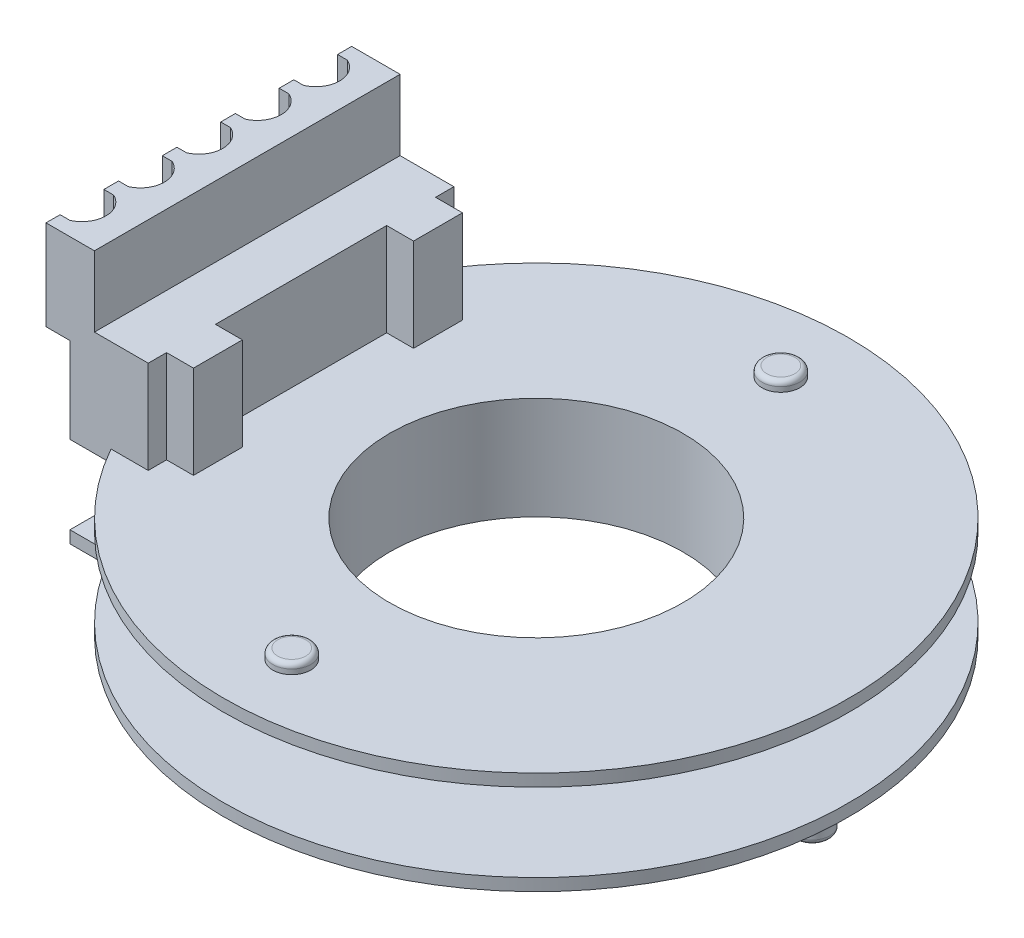
SolidWorks part; units mm, degrees
material "Полиамид ПА-6Б ТУ 6-05-988-93"
ref_plane "Спереди" through (0, 0, 0) normal (0, 0, 1) x (1, 0, 0)
ref_plane "Сверху" through (0, 0, 0) normal (0, 1, 0) x (1, 0, 0)
ref_plane "Справа" through (0, 0, 0) normal (1, 0, 0) x (0, 0, -1)
sketch "Эскиз1" plane through (0, 0, 0) normal (0, 0, 1) x (1, 0, 0)
  line L0 (7, 1.6) -> (7, -1.6)
  line L1 (7, -1.6) -> (12.775, -1.6)
  line L2 (12.775, -1.6) -> (12.775, -2.1)
  line L3 (12.775, -2.1) -> (6, -2.1)
  line L4 (6, -2.1) -> (6, 2.1)
  line L5 (6, 2.1) -> (12.775, 2.1)
  line L6 (12.775, 2.1) -> (12.775, 1.6)
  line L7 (12.775, 1.6) -> (7, 1.6)
  line L8 (6, 0) -> (0, 0) construction
  line L9 (0, 2.1) -> (0, -2.1) construction
  dimension "D1" = 6
  dimension "D2" = 0.5
  dimension "D3" = 1
  dimension "D4" = 4.2
  dimension "D5" = 12.775
revolve "Повернуть1" add sketch "Эскиз1" angle 360 about L9
sketch "Эскиз2" plane through (0, 2.1, 0) normal (0, 1, 0) x (1, 0, 0)
  line L0 (-12.82, 6.25) -> (-9.47, 6.25)
  line L1 (-9.47, 6.25) -> (-9.47, -6.25)
  line L2 (-9.47, -6.25) -> (-12.82, -6.25)
  line L5 (-12.82, -6.25) -> (-12.82, 6.25)
  line L8 (-9.47, 0) -> (0, 0) construction
  dimension "D2" = 12.5
  dimension "D4" = 3.35
  dimension "D5" = 9.47
extrude "Бобышка-Вытянуть1" add sketch "Эскиз2" along normal blind 3.8 and the other way blind 0.5
sketch "Эскиз4" plane through (0, 5.9, 0) normal (0, 1, 0) x (1, 0, 0)
  line L0 (-12.82, 6.25) -> (-12.82, -6.25) construction
  line L1 (-9.47, 6.25) -> (-8.52, 6.25)
  line L2 (-9.47, 6.25) -> (-9.47, -6.25)
  line L3 (-9.47, -6.25) -> (-8.52, -6.25)
  line L4 (-8.52, 6.25) -> (-8.52, -6.25)
  dimension "D1" = 4.3
extrude "Бобышка-Вытянуть2" add sketch "Эскиз4" against normal up to surface (3.8 mm away) up to face at (-6, 2.1, 0)
sketch "Эскиз6" plane through (0, 5.9, 0) normal (0, 1, 0) x (1, 0, 0)
  line L0 (-8.52, -6.25) -> (-8.52, 6.25) construction
  line L1 (-8.52, 6.25) -> (-9.62, 6.25)
  line L2 (-8.52, 6.25) -> (-8.52, 5.5)
  line L3 (-8.52, 5.5) -> (-9.62, 5.5)
  line L4 (-9.62, 6.25) -> (-9.62, 5.5)
  line L5 (-8.52, 3.5) -> (-9.62, 3.5)
  line L6 (-8.52, 3.5) -> (-8.52, -3.5)
  line L7 (-8.52, -3.5) -> (-9.62, -3.5)
  line L8 (-9.62, 3.5) -> (-9.62, -3.5)
  line L9 (-8.52, 0) -> (0, 0) construction
  line L10 (-8.52, -6.25) -> (-9.62, -6.25)
  line L11 (-8.52, -6.25) -> (-8.52, -5.5)
  line L12 (-8.52, -5.5) -> (-9.62, -5.5)
  line L13 (-9.62, -6.25) -> (-9.62, -5.5)
  point P19 (-8.52, 5.875)
  dimension "D1" = 2
  dimension "D2" = 0.75
  dimension "D3" = 1.1
extrude "Вырез-Вытянуть1" cut sketch "Эскиз6" against normal up to surface (3.8 mm away) up to face at (-6, 2.1, 0)
sketch "Эскиз7" plane through (0, 5.9, 0) normal (0, 1, 0) x (1, 0, 0)
  line L0 (-9.62, 6.25) -> (-12.82, 6.25) construction
  line L1 (-11.82, 6.25) -> (-13.8, 6.25)
  line L2 (-11.82, 6.25) -> (-11.82, -6.25)
  line L3 (-11.82, -6.25) -> (-13.8, -6.25)
  line L4 (-13.8, 6.25) -> (-13.8, -6.25)
  line L5 (-12.82, -6.25) -> (-9.62, -6.25) construction
  line L6 (-8.52, 3.5) -> (-8.52, 5.5) construction
  dimension "D1" = 3.3
  dimension "D2" = 1.98
extrude "Бобышка-Вытянуть3" add sketch "Эскиз7" along normal blind 2.88 and the other way blind 0.8
sketch "Эскиз8" plane through (-12.82, 0, 0) normal (-1, 0, 0) x (0, 0, 1)
  line L0 (-6.25, 1.6) -> (6.25, 1.6) construction
  circle A0 centre (-2.4, 2.45) radius 0.425
  circle A1 centre (0, 2.45) radius 0.425
  circle A2 centre (2.4, 2.45) radius 0.425
  dimension "D1" = 0.85
  dimension "D2" = 2.4
  dimension "D3" = 2.4
  dimension "D4" = 0.85
extrude "Бобышка-Вытянуть4" add sketch "Эскиз8" along normal blind 2.4 separate body
sketch "Эскиз9" plane through (0, 8.78, 0) normal (0, 1, 0) x (1, 0, 0)
  line L1 (-13.8, 6.25) -> (-13.8, -6.25) construction
  line L2 (-12.82, 6.25) -> (-12.82, -6.25) construction
  line L3 (-13.4, 3.284) -> (-13.8, 3.284)
  line L4 (-13.4, -1.4947) -> (-13.8, -1.4947)
  line L5 (-13.8, -1.4947) -> (-13.8, -3.284)
  line L6 (-13.4, 0.8947) -> (-13.8, 0.8947)
  line L7 (-13.8, 0.8947) -> (-13.8, -0.8947)
  line L8 (-13.4, 5.6733) -> (-13.8, 5.6733)
  line L9 (-13.8, 5.6733) -> (-13.8, 3.884)
  line L10 (-13.8, 3.884) -> (-13.4, 3.884)
  line L11 (-13.8, 3.284) -> (-13.8, 1.4947)
  line L12 (-13.8, 1.4947) -> (-13.4, 1.4947)
  line L13 (-13.8, -0.8947) -> (-13.4, -0.8947)
  line L14 (-13.8, -3.284) -> (-13.4, -3.284)
  line L15 (-13.4, -3.884) -> (-13.8, -3.884)
  line L16 (-13.8, -3.884) -> (-13.8, -5.6733)
  line L17 (-13.8, -5.6733) -> (-13.4, -5.6733)
  arc A0 (-13.4, 3.884) -> (-13.4, 5.6733) centre (-13.8, 4.7786) ccw
  arc A1 (-13.4, 1.4947) -> (-13.4, 3.284) centre (-13.8, 2.3893) ccw
  arc A2 (-13.4, -0.8947) -> (-13.4, 0.8947) centre (-13.8, 0) ccw
  arc A3 (-13.4, -3.284) -> (-13.4, -1.4947) centre (-13.8, -2.3893) ccw
  arc A4 (-13.4, -5.6733) -> (-13.4, -3.884) centre (-13.8, -4.7786) ccw
  dimension "D1" = 0.6
  dimension "D2" = 0.6
  dimension "D3" = 0.6
  dimension "D4" = 0.6
  dimension "D5" = 0.4
extrude "Вырез-Вытянуть2" cut sketch "Эскиз9" against normal up to surface (3.68 mm away) up to face at (-13.31, 5.1, 0)
sketch "Эскиз10" plane through (0, 2.1, 0) normal (0, 1, 0) x (1, 0, 0)
  circle A0 centre (0, 0) radius 10 construction
  circle A1 centre (0, 10) radius 0.775
  circle A2 centre (0, -10) radius 0.775
  dimension "D1" = 20
  dimension "D2" = 1.55
extrude "Бобышка-Вытянуть5" add sketch "Эскиз10" along normal blind 0.4
sketch "Эскиз11" plane through (0, -2.1, 0) normal (0, -1, 0) x (1, 0, 0)
  line L0 (-11.22, 5.35) -> (-11.22, -5.35) construction
  line L1 (-11.22, 0) -> (0, 0) construction
  circle A0 centre (0, -10) radius 0.775 construction
  circle A1 centre (0, 10) radius 0.775 construction
  circle A2 centre (0, -10) radius 0.775
  circle A3 centre (0, 10) radius 0.775
  circle A4 centre (11.28, 0) radius 0.725
  circle A5 centre (-11.22, 5.35) radius 0.725
  circle A6 centre (-11.22, -5.35) radius 0.725
  dimension "D3" = 1.45
  dimension "D1" = 11.22
  dimension "D2" = 10.7
  dimension "D4" = 11.28
extrude "Бобышка-Вытянуть6" add sketch "Эскиз11" along normal blind 0.4
sketch "Эскиз12" plane through (0, -2.5, 0) normal (0, -1, 0) x (1, 0, 0)
  circle A0 centre (11.28, 0) radius 0.725 construction
  circle A1 centre (-11.22, -5.35) radius 0.725 construction
  circle A2 centre (-11.22, 5.35) radius 0.725 construction
  circle A3 centre (11.28, 0) radius 0.725
  circle A4 centre (-11.22, -5.35) radius 0.725
  circle A5 centre (-11.22, 5.35) radius 0.725
extrude "Бобышка-Вытянуть7" add sketch "Эскиз12" along normal blind 0.85
fillet "Скругление1" radius 0.2 7 edges at (-0.775, 2.5, 10) (-0.775, 2.5, -10) (12.005, -3.35, 0) (-10.495, -3.35, 5.35) (-10.495, -3.35, -5.35) (0.775, -2.5, -10) (0.775, -2.5, 10)
sketch "Эскиз13" plane through (0, -2.1, 0) normal (0, -1, 0) x (1, 0, 0)
  line L0 (-12.82, 6.25) -> (-12.82, -6.25)
  line L1 (-12.82, -6.25) -> (-10.495, -6.25)
  line L2 (-10.495, -6.25) -> (-10.495, 6.25)
  line L3 (-10.495, 6.25) -> (-12.82, 6.25)
  arc A0 (-11.7946, 4.9079) -> (-11.2382, 6.0748) centre (-11.22, 5.35) ccw construction
extrude "Бобышка-Вытянуть8" add sketch "Эскиз13" against normal up to surface (0.5 mm away) up to face at (-7, -1.6, 0)
